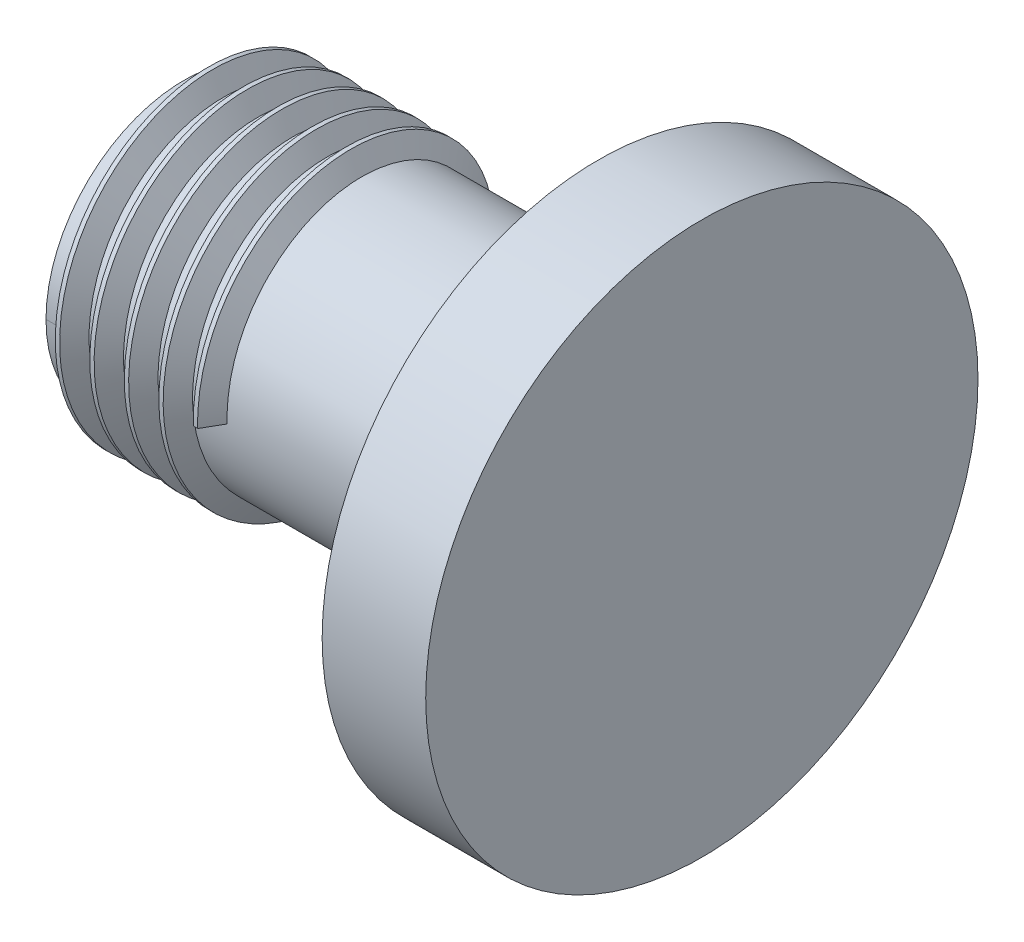
SolidWorks part; units mm, degrees
ref_plane "Ön Düzlem" through (0, 0, 0) normal (0, 0, 1) x (1, 0, 0)
ref_plane "Üst Düzlem" through (0, 0, 0) normal (0, 1, 0) x (1, 0, 0)
ref_plane "Sağ Düzlem" through (0, 0, 0) normal (1, 0, 0) x (0, 0, -1)
sketch "Çizim1" plane through (0, 0, 0) normal (0, 0, 1) x (1, 0, 0)
  line L0 (-52.0255, -13.3001) -> (-40.0255, -13.3001)
  line L1 (-52.0255, -13.3001) -> (-52.0255, -9.3001)
  line L2 (-52.0255, -9.3001) -> (-37.0255, -9.3001)
  line L3 (-37.0255, -9.3001) -> (-37.0255, -17.3001)
  line L4 (-40.0255, -13.3001) -> (-40.0255, -17.3001)
  line L5 (-40.0255, -17.3001) -> (-37.0255, -17.3001)
  dimension "D1" = 8
  dimension "D2" = 4
  dimension "D3" = 15
  dimension "D4" = 12
revolve "Döndür1" add sketch "Çizim1" angle 360 about L2
thread "Diş1" pitch 1 method extrude profile "Diş Profili1" start angle 0, offset 0, length 4.5, pitch 1, diameter 8
ref_plane "Düzlem1" through (-52.0255, -9.3001, -4) normal (0, -1, 0) x (0, 0, -1)
sketch "Diş Profili1" plane through (-52.0255, -9.3001, -4) normal (0, -1, 0) x (0, 0, -1)
  line L0 (0, 0) -> (0, 1) construction
  line L1 (0, 0) -> (0.5413, 0.3125)
  line L2 (0.5413, 0.3125) -> (0.5413, 0.4375)
  line L3 (0.5413, 0.4375) -> (0, 0.75)
  line L4 (0.5413, 0.375) -> (0, 0.375) construction
  line L11 (0, 0) -> (0, 0.75)
  point P2 (0, 0)
  dimension "Pitch" = 1
  dimension "Profile_Angle" = 60
  dimension "Profile_Land" = 0.125
  dimension "Profile_Height" = 0.5413
